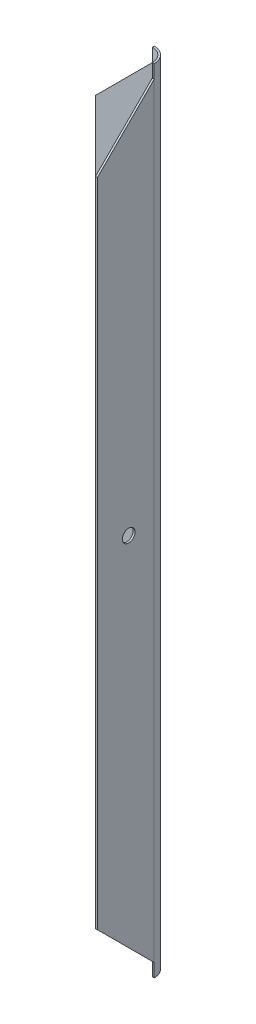
SolidWorks part; units mm, degrees
ref_plane "Front" through (0, 0, 0) normal (0, 0, 1) x (1, 0, 0)
ref_plane "Top" through (0, 0, 0) normal (0, 1, 0) x (1, 0, 0)
ref_plane "Right" through (0, 0, 0) normal (1, 0, 0) x (0, 0, -1)
sketch "Sketch1" plane through (0, 0, 0) normal (1, 0, 0) x (0, 0, -1)
  line L0 (0, -255) -> (0, 255)
  line L1 (0, 0) -> (55, 0) construction
  line L2 (55, 310) -> (55, -310)
  line L3 (55, 310) -> (0, 255)
  line L4 (0, -255) -> (55, -310)
  line L6 (55, 310) -> (56.5, 310)
  line L7 (55, 310) -> (55, -310)
  line L8 (55, -310) -> (56.5, -310)
  line L9 (56.5, 310) -> (56.5, -310)
  point P4 (0, 0)
  point P9 (55, 0)
  dimension "D1" = 620
  dimension "D2" = 55
  dimension "D3" = 45
  dimension "D4" = 1.5
extrude "Boss-Extrude1" add sketch "Sketch1" along normal blind 1.5 contours L0 L1 L2 L3 | L1 L0 L4 L7 | L9 L6 L2 L7 L8 region at (0, -141.6962, -28.3923) region at (0, 141.6962, -28.3923) region at (0, 0, -55.75)
sketch "Sketch2" plane through (0, 0, -56.5) normal (0, 0, -1) x (-1, 0, 0)
  line L0 (0, 0) -> (55, 0) construction
  line L1 (55, 255) -> (55, -255)
  line L2 (55, 255) -> (0, 310)
  line L3 (55, -255) -> (0, -310)
  line L4 (0, -310) -> (0, 310)
  point P6 (55, 0)
  dimension "D1" = 55
  dimension "D2" = 45
extrude "Boss-Extrude3" add sketch "Sketch2" against normal blind 1.5
sketch "Sketch5" plane through (0, -310, 0) normal (0, -1, 0) x (1, 0, 0)
  line L0 (0, 0) -> (0, -55) construction
  line L1 (0, -55) -> (-55, -55) construction
  line L2 (-10.5, -55) -> (-10.5, -56.5)
  line L3 (0, -44.5) -> (1.5, -44.5)
  line L4 (-10.5, -56.5) -> (1.5, -56.5)
  line L5 (1.5, -56.5) -> (1.5, -44.5)
  arc A0 (-10.5, -55) -> (0, -44.5) centre (-10.5, -44.5) ccw
  arc A1 (-10.5, -56.5) -> (1.5, -44.5) centre (-10.5, -44.5) ccw
  circle A2 centre (-10.5, -44.5) radius 12 construction
  circle A3 centre (-10.5, -44.5) radius 10.5 construction
  line M3 (0, -55) -> (0, -56.5)
  line M4 (0, -56.5) -> (1.5, -56.5)
  line M5 (1.5, -56.5) -> (1.5, -55)
  line M6 (1.5, -55) -> (0, -55)
  dimension "D1" = 21
  dimension "D2" = 1.5
extrude "Cut-Extrude1" cut sketch "Sketch5" against normal through all both and the other way through all contours A1 L4 L5 M3 M6 | M6 M3 M4 M5 region at (-1.332, -310, -53.668) region at (0.75, -310, -55.75)
extrude "Boss-Extrude4" add sketch "Sketch5<3>" against normal blind 620 contours L2 A1 L3 A0 region at (-2.9554, -310, -52.0446)
sketch "Sketch5<3>" plane through (0, -310, 0) normal (0, -1, 0) x (1, 0, 0) same geometry as "Sketch5"
sketch "Sketch6" plane through (1.5, 0, 0) normal (1, 0, 0) x (0, 0, -1)
  line L0 (44.5, 299.5) -> (44.5, -299.5) construction
  line L1 (56.5, 310) -> (44.5, 310) construction
  circle A0 centre (24.5, 0) radius 5
  dimension "D1" = 10
  dimension "D2" = 20
  dimension "D3" = 310
extrude "Cut-Extrude2" cut sketch "Sketch6" against normal through all both
sketch "Sketch7" plane through (0, 0, -56.5) normal (0, 0, -1) x (-1, 0, 0)
  line L0 (10.5, 299.5) -> (10.5, -299.5) construction
  circle A0 centre (30.5, 0) radius 5
  dimension "D1" = 10
  dimension "D2" = 20
  dimension "D3" = 310
extrude "Cut-Extrude3" cut sketch "Sketch7" against normal through all both
